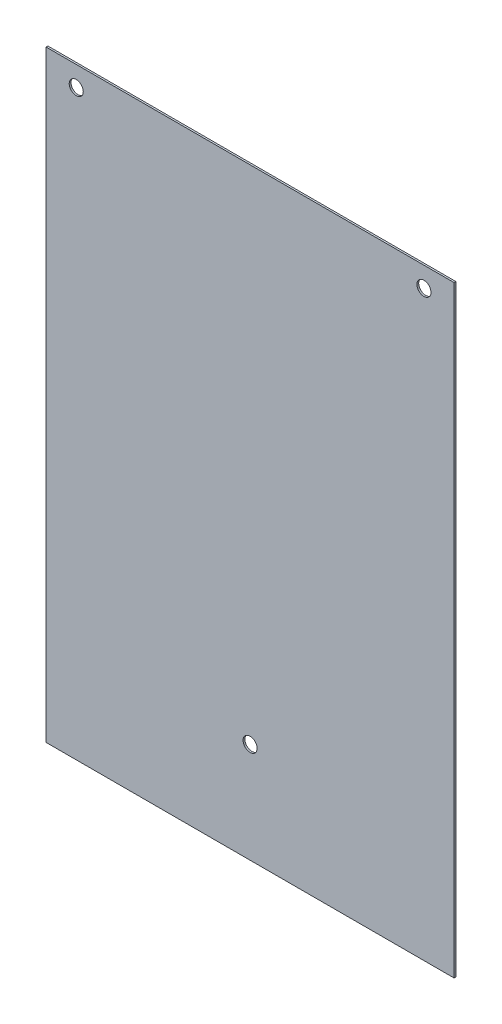
SolidWorks part; units mm, degrees
ref_plane "前视基准面" through (0, 0, 0) normal (0, 0, 1) x (1, 0, 0)
ref_plane "上视基准面" through (0, 0, 0) normal (0, 1, 0) x (1, 0, 0)
ref_plane "右视基准面" through (0, 0, 0) normal (1, 0, 0) x (0, 0, -1)
sketch "草图1" plane through (0, 0, 0) normal (0, 0, 1) x (1, 0, 0)
  line L1 (-101.6, 150) -> (101.6, 150)
  line L2 (-101.6, 150) -> (-101.6, -150)
  line L3 (-101.6, -150) -> (101.6, -150)
  line L4 (101.6, 150) -> (101.6, -150)
  line L5 (-101.6, 150) -> (101.6, -150) construction
  line L6 (-101.6, -150) -> (101.6, 150) construction
  point P0 (0, 0)
  dimension "D1" = 203.2
  dimension "D2" = 300
extrude "凸台-拉伸1" add sketch "草图1" along normal blind 0.9
sketch "草图2" plane through (0, 0, 0.9) normal (0, 0, 1) x (1, 0, 0)
  line L0 (101.6, 150) -> (-101.6, 150) construction
  line L1 (-101.6, 150) -> (-101.6, -150) construction
  line L2 (101.6, -150) -> (101.6, 150) construction
  line L3 (-101.6, -150) -> (101.6, -150) construction
  circle A0 centre (-86.6, 140) radius 3.5
  circle A1 centre (86.6, 140) radius 3.5
  circle A8 centre (0, -100) radius 3.5
  dimension "D1" = 10
  dimension "D2" = 10
  dimension "D4" = 15
  dimension "D3" = 15
  dimension "D5" = 50
extrude "Cut-Extrude1" cut sketch "草图2" against normal up to surface (0.9 mm away) up to face at (0, 0, 0)
